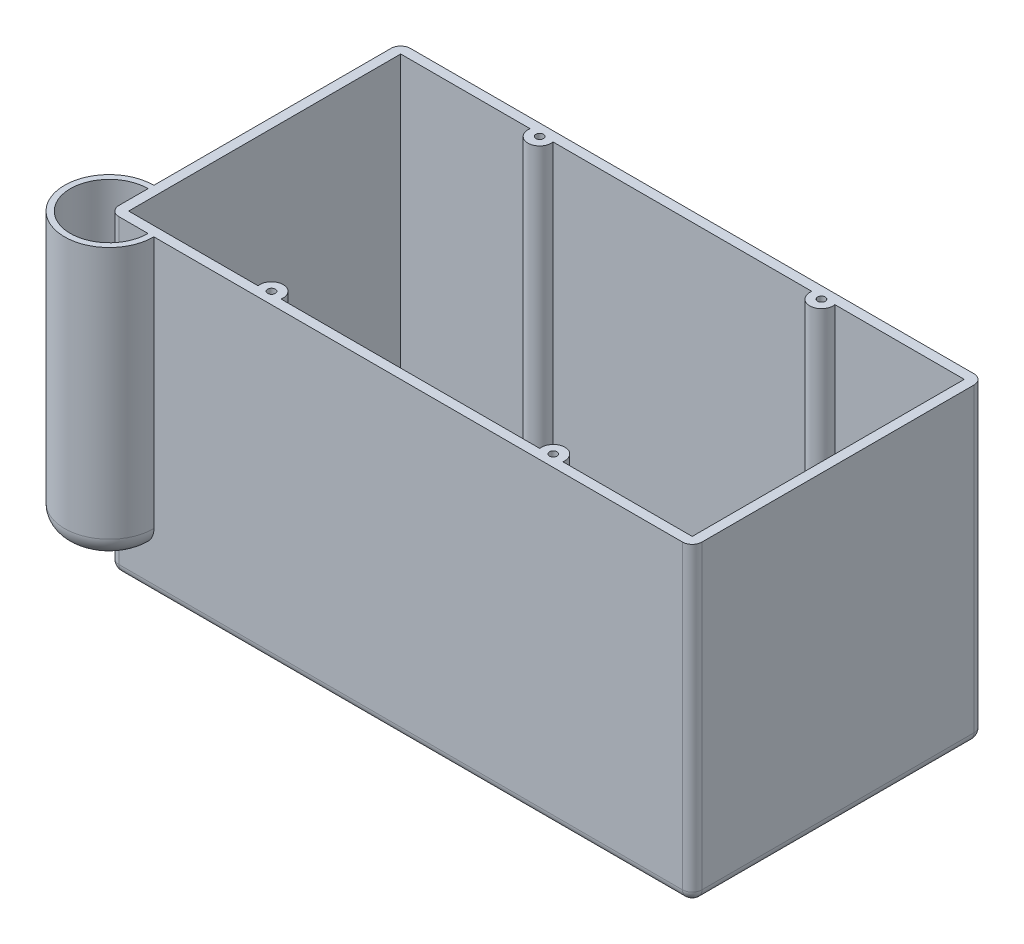
SolidWorks part; units mm, degrees
ref_plane "Plan de face" through (0, 0, 0) normal (0, 0, 1) x (1, 0, 0)
ref_plane "Plan de dessus" through (0, 0, 0) normal (0, 1, 0) x (1, 0, 0)
ref_plane "Plan de droite" through (0, 0, 0) normal (1, 0, 0) x (0, 0, -1)
sketch "Esquisse1" plane through (0, 0, 0) normal (0, 1, 0) x (1, 0, 0)
  line L1 (150, -75) -> (-150, -75)
  line L2 (150, -75) -> (150, 75)
  line L3 (150, 75) -> (-150, 75)
  line L4 (-150, -75) -> (-150, 75)
  line L5 (150, -75) -> (-150, 75) construction
  line L6 (150, 75) -> (-150, -75) construction
  point P0 (0, 0)
  dimension "D1" = 300
  dimension "D2" = 150
extrude "Boss.-Extru.1" add sketch "Esquisse1" along normal blind 5
sketch "Esquisse3" plane through (0, 5, 0) normal (0, 1, 0) x (1, 0, 0)
  line L8 (150, -75) -> (150, 75) construction
  line L9 (150, 75) -> (-150, 75) construction
  line L10 (-150, 75) -> (-150, -75) construction
  line L11 (-150, -75) -> (150, -75) construction
  line L12 (-145, 70) -> (-145, -70)
  line L13 (145, 70) -> (-145, 70)
  line L14 (145, -70) -> (145, 70)
  line L15 (-145, -70) -> (145, -70)
  line L16 (-145, 70) -> (-145, -70)
  line L17 (145, 70) -> (-145, 70)
  line L18 (145, -70) -> (145, 70)
  line L19 (-145, -70) -> (145, -70)
  line L20 (150, -75) -> (150, 75)
  line L21 (150, 75) -> (-150, 75)
  line L22 (-150, 75) -> (-150, -75)
  line L23 (-150, -75) -> (150, -75)
  point P0 (0, 0)
  dimension "D1" = 5
extrude "Boss.-Extru.2" add sketch "Esquisse3" along normal blind 155
sketch "Esquisse4" plane through (0, 5, 0) normal (0, 1, 0) x (1, 0, 0)
  line L0 (0, 106.1654) -> (0, -98.0058) construction
  line L1 (-145, 70) -> (0, 70) construction
  line L2 (145, 70) -> (-145, 70) construction
  line L3 (150, 75) -> (-150, 75) construction
  line L5 (-187.7557, 0) -> (177.3664, 0) construction
  circle A1 centre (-72.5, 69) radius 6
  circle A2 centre (72.5, 69) radius 6
  circle A3 centre (72.5, -69) radius 6
  circle A4 centre (-72.5, -69) radius 6
  dimension "D1" = 6
  dimension "D2" = 12
extrude "Boss.-Extru.4" add sketch "Esquisse4" along normal blind 155
sketch "Esquisse5" plane through (0, 160, 0) normal (0, 1, 0) x (1, 0, 0)
  line L0 (0, 103.7967) -> (0, -102.913) construction
  line L1 (-172.8625, 0) -> (192.506, 0) construction
  line L2 (-145, 70) -> (0, 70) construction
  circle A0 centre (-72.5, 69) radius 1.95
  circle A1 centre (72.5, 69) radius 1.95
  circle A2 centre (72.5, -69) radius 1.95
  circle A3 centre (-72.5, -69) radius 1.95
  dimension "D1" = 3.9
extrude "Enlèv. mat.-Extru.1" cut sketch "Esquisse5" against normal blind 6
sketch "Esquisse6" plane through (0, 0, 75) normal (0, 0, 1) x (1, 0, 0)
  line L0 (-150, 160) -> (-150, 0) construction
  line L1 (-150, 0) -> (150, 0) construction
  circle A0 centre (-150, 50) radius 20
  dimension "D1" = 40
  dimension "D2" = 50
extrude "Enlèv. mat.-Extru.2" cut sketch "Esquisse6" against normal blind 5
sketch "Esquisse7" plane through (-150, 0, 0) normal (-1, 0, 0) x (0, 0, 1)
  line L0 (75, 30) -> (75, 70) construction
  circle A0 centre (75, 50) radius 20
extrude "Enlèv. mat.-Extru.3" cut sketch "Esquisse7" against normal blind 5
sketch "Esquisse8" plane through (0, 160, 0) normal (0, 1, 0) x (1, 0, 0)
  circle A0 centre (-150, -75) radius 20
  circle A1 centre (-150, -75) radius 23
  dimension "D1" = 3
extrude "Boss.-Extru.5" add sketch "Esquisse8" against normal blind 140
sketch "Esquisse9" plane through (0, 20, 0) normal (0, -1, 0) x (1, 0, 0)
  circle A0 centre (-150, 75) radius 20
extrude "Boss.-Extru.6" add sketch "Esquisse9" against normal blind 3
sketch "Esquisse10" plane through (0, 160, 0) normal (0, 1, 0) x (1, 0, 0)
  line L0 (-150, -52) -> (-150, -75)
  line L1 (-150, -75) -> (-127, -75)
  arc A0 (-150, -52) -> (-127, -75) centre (-150, -75) cw
extrude "Boss.-Extru.7" add sketch "Esquisse10" against normal blind 3
fillet "Congé1" radius 10 1 edges at (-166.2635, 20, 91.2635)
fillet "Congé2" radius 5 4 edges at (0, 0, -75) (150, 0, 0) (0, 0, 75) (-150, 0, 0)
fillet "Congé3" radius 5 9 edges at (-148.5355, 1.4645, 73.5355) (-148.5355, 1.4645, -73.5355) (148.5355, 1.4645, -73.5355) (148.5355, 1.4645, 73.5355) (-150, 12.5, 75) (-150, 115, 75) (-150, 82.5, -75) (150, 82.5, -75) (150, 82.5, 75)
sketch "Esquisse12" plane through (0, 160, 0) normal (0, 1, 0) x (1, 0, 0)
  line L1 (-127.5501, -70) -> (-145, -70)
  line L2 (-127.5501, -70) -> (-127.5501, -52.5501)
  line L3 (-127.5501, -52.5501) -> (-145, -52.5501)
  line L4 (-145, -70) -> (-145, -52.5501)
extrude "Enlèv. mat.-Extru.5" cut sketch "Esquisse12" against normal blind 152
